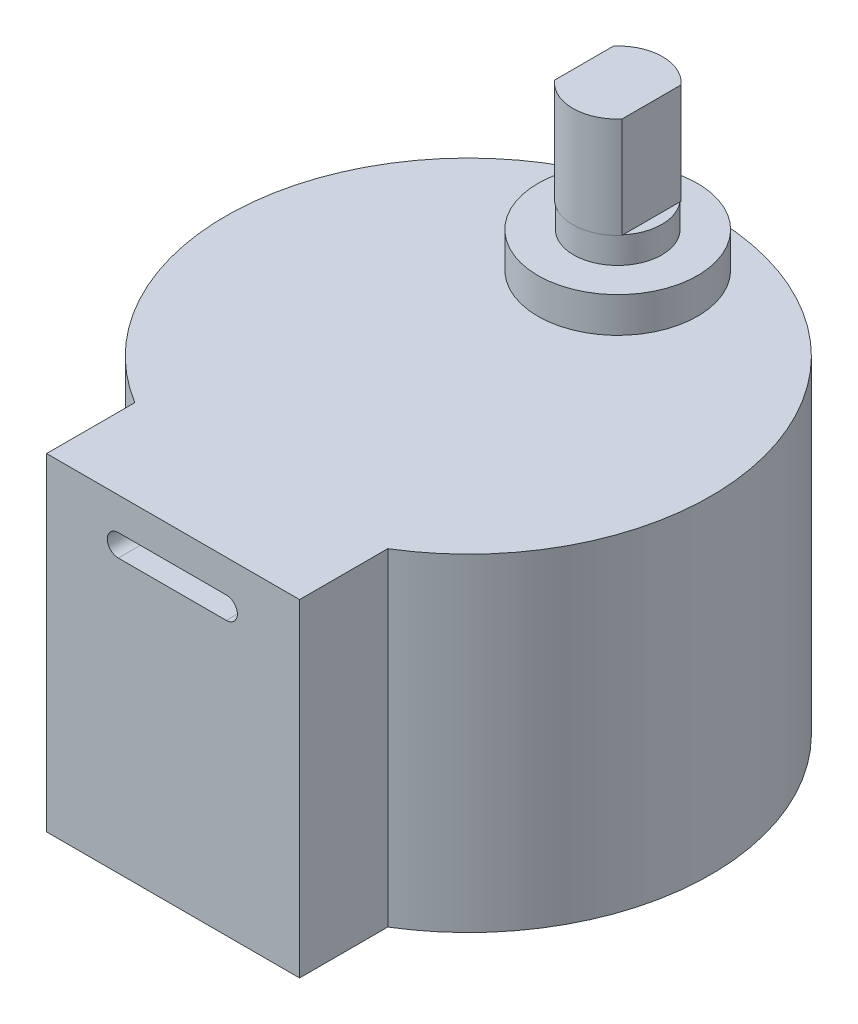
SolidWorks part; units mm, degrees
ref_plane "Front Plane" through (0, 0, 0) normal (0, 0, 1) x (1, 0, 0)
ref_plane "Top Plane" through (0, 0, 0) normal (0, 1, 0) x (1, 0, 0)
ref_plane "Right Plane" through (0, 0, 0) normal (1, 0, 0) x (0, 0, -1)
sketch "Sketch1" plane through (0, 0, 0) normal (0, 1, 0) x (1, 0, 0)
  line L2 (-7.2834, -11.9211) -> (-7.2834, -17.0011)
  line L3 (-7.2834, -17.0011) -> (7.2835, -17.0011)
  line L4 (7.2835, -11.9211) -> (7.2835, -17.0011)
  arc A0 (7.2835, -11.9211) -> (-7.2834, -11.9211) centre (0, 0) ccw
  dimension "D1" = 27.94
  dimension "D2" = 14.5669
  dimension "D3" = 7.2835
  dimension "D4" = 5.08
extrude "Boss-Extrude1" add sketch "Sketch1" along normal blind 18.8722
sketch "Sketch3" plane through (0, 18.8722, 0) normal (0, 1, 0) x (1, 0, 0)
  line L0 (7.2835, -17.0011) -> (7.2835, -11.9211) construction
  circle A1 centre (0.0191, 8.5852) radius 4.5974
  arc A2 (7.2835, -11.9211) -> (-7.2834, -11.9211) centre (0, 0) ccw construction
  circle A3 centre (0.0191, 8.5852) radius 2.54
  point P5 (0, 13.97)
  dimension "D1" = 9.1948
  dimension "D2" = 5.3848
  dimension "D4" = 5.08
  dimension "D3" = 7.2644
extrude "Boss-Extrude2" add sketch "Sketch3" along normal blind 2.032
extrude "Boss-Extrude3" add sketch "Sketch3<2>" along normal blind 2.032
sketch "Sketch3<2>" plane through (0, 18.8722, 0) normal (0, 1, 0) x (1, 0, 0) same geometry as "Sketch3"
sketch "Sketch4" plane through (0, 18.8722, 0) normal (0, 1, 0) x (1, 0, 0)
  circle A0 centre (0.0191, 8.5852) radius 2.54
extrude "Boss-Extrude4" add sketch "Sketch4" along normal blind 3.556
sketch "Sketch5" plane through (0, 22.4282, 0) normal (0, 1, 0) x (1, 0, 0)
  line L0 (-1.9215, 10.287) -> (-1.9215, 6.8834)
  line L1 (1.9596, 10.287) -> (1.9596, 6.8834)
  arc A0 (-1.9215, 6.8834) -> (1.9596, 6.8834) centre (0.0191, 8.5852) ccw
  arc A1 (1.9596, 10.287) -> (-1.9215, 10.287) centre (0.0191, 8.5852) ccw
  dimension "D3" = 2.581
  dimension "D1" = 3.4036
  dimension "D2" = 3.4036
extrude "Boss-Extrude5" add sketch "Sketch5" along normal blind 5.8039
sketch "Sketch6" plane through (0, 0, 17.0011) normal (0, 0, 1) x (1, 0, 0)
  line L0 (-3.1559, 16.3593) -> (3.0671, 16.3593) construction
  line L1 (-3.1559, 16.9943) -> (3.0671, 16.9943)
  line L2 (-3.1559, 15.7243) -> (3.0671, 15.7243)
  line L3 (-7.2834, 18.8722) -> (-7.2834, 0) construction
  arc A0 (-3.1559, 16.9943) -> (-3.1559, 15.7243) centre (-3.1559, 16.3593) ccw
  arc A1 (3.0671, 15.7243) -> (3.0671, 16.9943) centre (3.0671, 16.3593) ccw
  point P2 (-0.0444, 16.3593)
  dimension "D1" = 6.223
  dimension "D2" = 7.239
  dimension "D3" = 1.27
extrude "Cut-Extrude1" cut sketch "Sketch6" against normal blind 7.62
